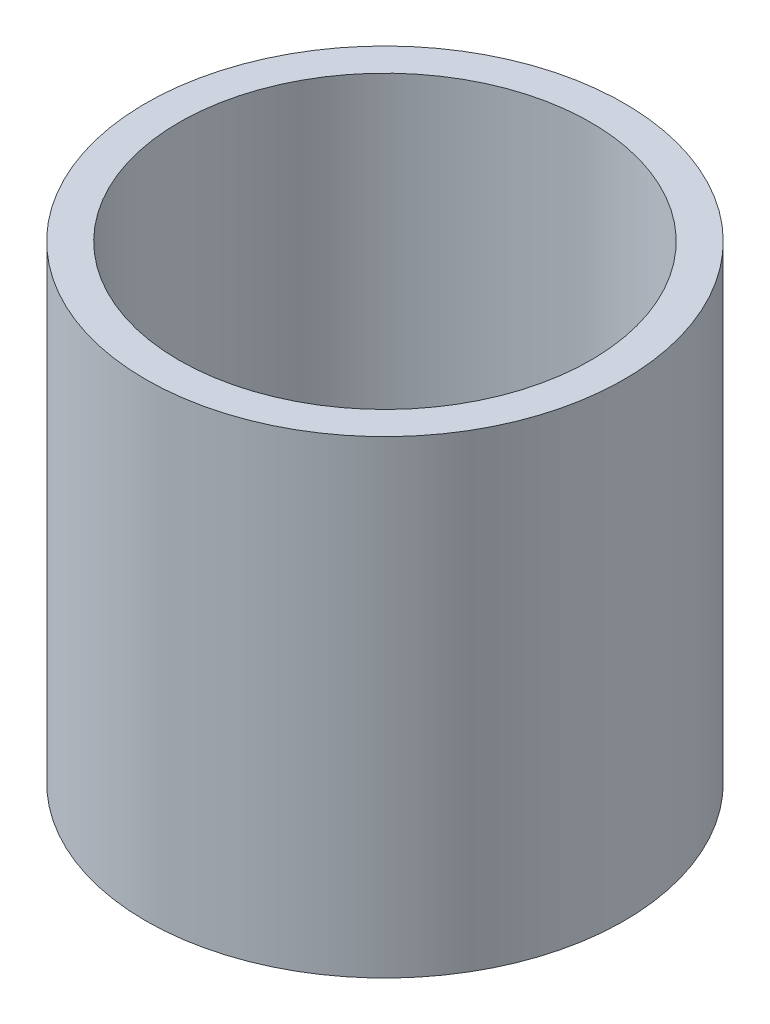
SolidWorks part; units mm, degrees
ref_plane "Front Plane" through (0, 0, 0) normal (0, 0, 1) x (1, 0, 0)
ref_plane "Top Plane" through (0, 0, 0) normal (0, 1, 0) x (1, 0, 0)
ref_plane "Right Plane" through (0, 0, 0) normal (1, 0, 0) x (0, 0, -1)
sketch "Sketch1" plane through (0, 0, 0) normal (0, 1, 0) x (1, 0, 0)
  circle A0 centre (0, 0) radius 27.5
  dimension "SLEEVE_OD" = 55
extrude "Boss-Extrude1" add sketch "Sketch1" along normal blind 53.8997
sketch "Sketch2" plane through (0, 0, 0) normal (0, 1, 0) x (1, 0, 0)
  circle A0 centre (0, 0) radius 23.6749
  dimension "BORE_D" = 47.3497
extrude "Cut-Extrude1" cut sketch "Sketch2" along normal through all
chamfer "Chamfer1" distance 1.9555 angle 45 rebuild error yes
